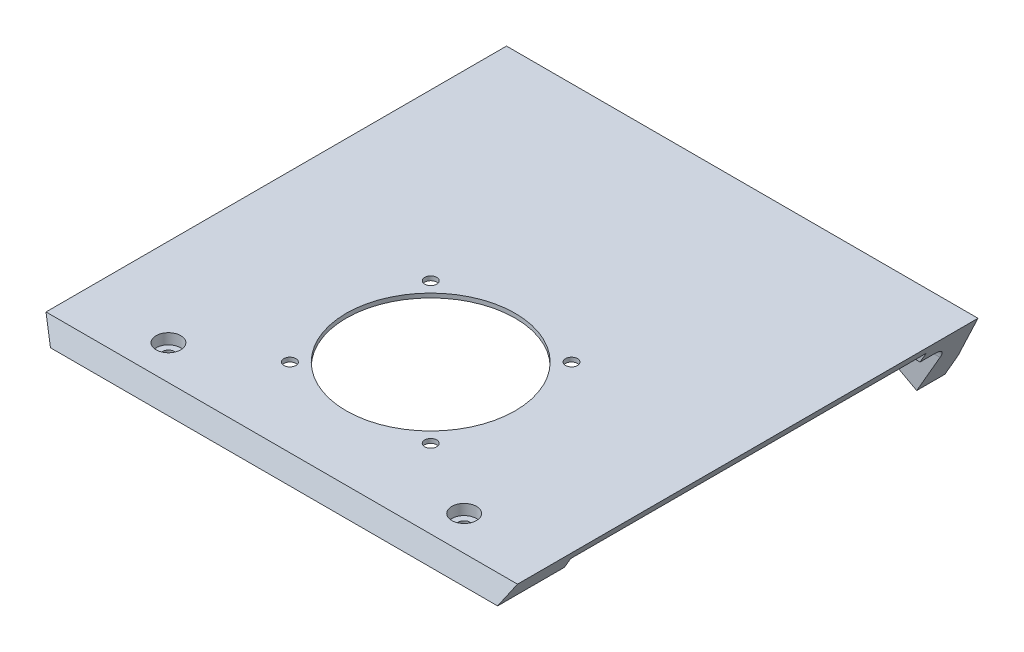
SolidWorks part; units mm, degrees
ref_plane "Front Plane" through (0, 0, 0) normal (0, 0, 1) x (1, 0, 0)
ref_plane "Top Plane" through (0, 0, 0) normal (0, 1, 0) x (1, 0, 0)
ref_plane "Right Plane" through (0, 0, 0) normal (1, 0, 0) x (0, 0, -1)
sketch "Sketch1" plane through (0, 0, 0) normal (0, 1, 0) x (1, 0, 0)
  line L0 (0, 64) -> (0, -64) construction
  line L1 (-63.5, 64) -> (63.5, 64)
  line L2 (-63.5, 64) -> (-63.5, -64)
  line L3 (-63.5, -64) -> (63.5, -64)
  line L4 (63.5, 64) -> (63.5, -64)
  line L5 (-63.5, 64) -> (63.5, -64) construction
  line L6 (-63.5, -64) -> (63.5, 64) construction
  circle A0 centre (-42, -52) radius 1.7
  circle A1 centre (42, -52) radius 1.7
  point P0 (0, 0)
  dimension "D7" = 3.4
  dimension "D8" = 3.4
  dimension "D1" = 127
  dimension "D2" = 12
  dimension "D3" = 12
  dimension "D4" = 42
  dimension "D5" = 42
  dimension "D6" = 128
extrude "Boss-Extrude2" add sketch "Sketch1" along normal blind 6
sketch "Sketch2" plane through (0, 0, -64) normal (0, 0, -1) x (-1, 0, 0)
  line L0 (0, 0) -> (0, -111) construction
  line L1 (-63.5, 6) -> (-63.5, -21.1793)
  line L2 (63.5, 6) -> (63.5, -21.1793)
  line L4 (63.5, 6) -> (-63.5, 6)
  arc A1 (63.5, -21.1793) -> (-63.5, -21.1793) centre (0, -111) ccw
  dimension "D2" = 220
extrude "Boss-Extrude3" add sketch "Sketch2" along normal blind 8
sketch "Sketch3" plane through (0, 6, 0) normal (0, 1, 0) x (1, 0, 0)
  circle A0 centre (42, -52) radius 3.5
  circle A1 centre (-42, -52) radius 3.5
  dimension "D1" = 7
  dimension "D2" = 7
extrude "Cut-Extrude1" cut sketch "Sketch3" against normal blind 3
fillet "Chamfer1" radius 3 1 edges at (0, 6, -72)
draft "Draft2" type of draft neutral plane draft angle 30 neutral plane "Top Plane" faces to draft 1 face at (-63.5, -5.6227, -30.4286) neutral plane through (0, 0, 0) neutral plane normal (0, 1, 0) reverse direction yes parameters "D1"=30
draft "Draft3" type of draft neutral plane draft angle 30 neutral plane "Top Plane" faces to draft 1 face at (63.5, -5.6227, -30.4286) neutral plane through (0, 0, 0) neutral plane normal (0, 1, 0) reverse direction yes parameters "D1"=30
fillet "Fillet5" radius 4 1 edges at (0, 0, -64)
draft "Draft4" type of draft neutral plane draft angle 20 neutral plane "Top Plane" faces to draft 1 face at (0, 3, 64) neutral plane through (0, 0, 0) neutral plane normal (0, 1, 0) parameters "D1"=20
sketch "Sketch4" plane through (0, 0, 0) normal (0, -1, 0) x (1, 0, 0)
  line L8 (-63.5, 64) -> (63.5, 64) construction
  line L9 (-83.5, 45) -> (83.5, 45)
  line L10 (-83.5, 45) -> (-83.5, -56)
  line L11 (-83.5, -56) -> (83.5, -56)
  line L12 (83.5, 45) -> (83.5, -56)
  line L13 (-63.5, -60) -> (-25.5147, -60) construction
  line L14 (-63.5, -60) -> (-63.5, 64) construction
  line L15 (63.5, 64) -> (63.5, -60) construction
  dimension "D1" = 19
  dimension "D2" = 4
  dimension "D3" = 20
  dimension "D4" = 20
extrude "Cut-Extrude2" cut sketch "Sketch4" against normal blind 3
sketch "Sketch7" plane through (0, 3, 0) normal (0, -1, 0) x (1, 0, 0)
  line L0 (0, 45) -> (0, -38.0044) construction
  line L1 (65.2321, 45) -> (-65.2321, 45) construction
  line L2 (-27, 45) -> (-27, -9)
  line L3 (63.5, 45) -> (-63.5, 45) construction
  line L4 (27, 45) -> (27, -9)
  line L5 (-27, 45) -> (27, 45)
  line L6 (-27, -9) -> (27, -9)
  dimension "D1" = 27
  dimension "D2" = 27
  dimension "D3" = 54
  dimension "D4" = 54
sketch "Sketch5" plane through (0, 3, 0) normal (0, -1, 0) x (1, 0, 0)
  line L0 (65.2321, 45) -> (-65.2321, 45) construction
  circle A0 centre (0, 19.5) radius 24
  circle A1 centre (20, 39.5) radius 1.7
  circle A2 centre (20, -0.5) radius 1.7
  circle A3 centre (-20, -0.5) radius 1.7
  circle A4 centre (-20, 39.5) radius 1.7
  point P4 (0, 45)
  dimension "D1" = 48
  dimension "D3" = 3.4
  dimension "D2" = 25.5
  dimension "D4" = 20
  dimension "D5" = 20
  dimension "D6" = 4
extrude "Cut-Extrude3" cut sketch "Sketch7" against normal blind 1.8
extrude "Cut-Extrude4" cut sketch "Sketch5" against normal blind 3
